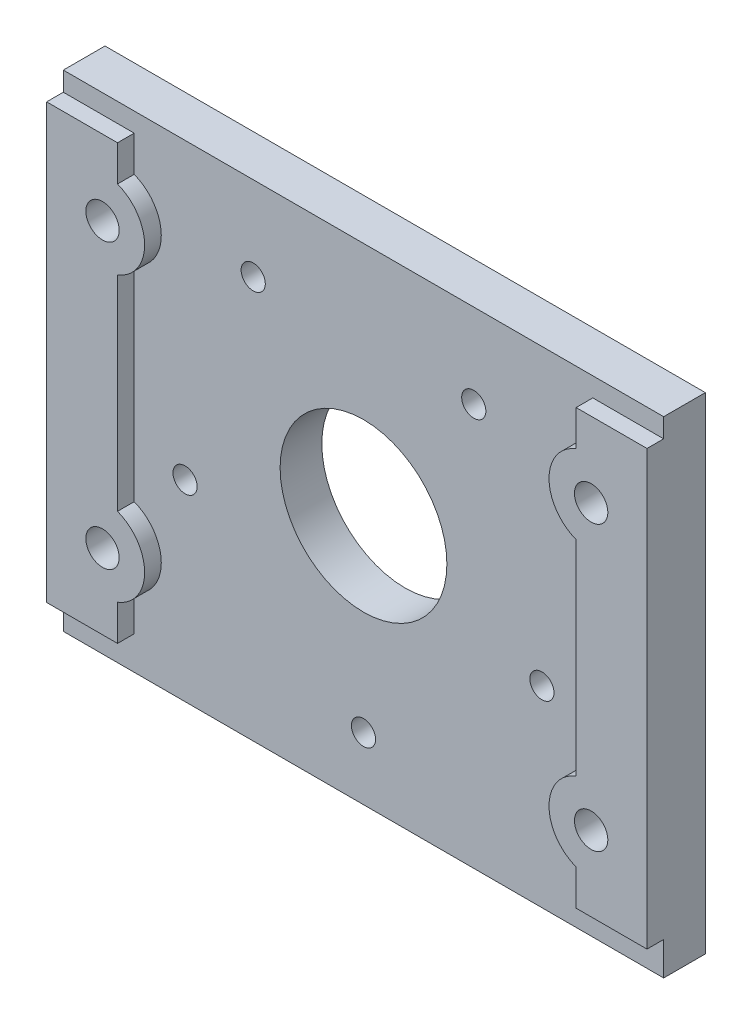
SolidWorks part; units mm, degrees
ref_plane "Front Plane" through (0, 0, 0) normal (0, 0, 1) x (1, 0, 0)
ref_plane "Top Plane" through (0, 0, 0) normal (0, 1, 0) x (1, 0, 0)
ref_plane "Right Plane" through (0, 0, 0) normal (1, 0, 0) x (0, 0, -1)
ref_plane "Plane1" through (0, 0, 280) normal (0, 0, 1) x (1, 0, 0)
sketch "Sketch1" plane through (0, 0, 280) normal (0, 0, 1) x (1, 0, 0)
  line L0 (264, 270) -> (336, 270)
  line L1 (336, 270) -> (336, 328.3)
  line L2 (336, 328.3) -> (264, 328.3)
  line L3 (264, 328.3) -> (264, 270)
  circle A0 centre (300, 300) radius 10
  circle A1 centre (286.7748, 318.2029) radius 1.45
  circle A2 centre (278.6012, 293.0471) radius 1.45
  circle A3 centre (300, 277.5) radius 1.45
  circle A4 centre (321.3988, 293.0471) radius 1.45
  circle A5 centre (313.2252, 318.2029) radius 1.45
extrude "Boss-Extrude1" add sketch "Sketch1" along normal blind 5
sketch "Sketch2" plane through (0, 0, 280) normal (0, 0, 1) x (1, 0, 0)
  line L0 (264, 274) -> (272.5, 274)
  line L1 (272.5, 274) -> (272.5, 326)
  line L2 (272.5, 326) -> (264, 326)
  line L3 (264, 326) -> (264, 274)
extrude "Boss-Extrude2" add sketch "Sketch2" along normal blind 7
sketch "Sketch3" plane through (0, 0, 280) normal (0, 0, 1) x (1, 0, 0)
  circle A0 centre (270.7, 283) radius 5.05
extrude "Boss-Extrude3" add sketch "Sketch3" along normal blind 7
sketch "Sketch4" plane through (0, 0, 280) normal (0, 0, 1) x (1, 0, 0)
  circle A0 centre (270.7, 317) radius 5.05
extrude "Boss-Extrude4" add sketch "Sketch4" along normal blind 7
ref_plane "Plane2" through (0, 0, 280.3) normal (0, 0, 1) x (1, 0, 0)
sketch "Sketch5" plane through (0, 0, 280.3) normal (0, 0, 1) x (1, 0, 0)
  circle A0 centre (270.7, 283) radius 2
  circle A1 centre (270.7, 317) radius 2
extrude "Cut-Extrude1" cut sketch "Sketch5" along normal blind 6.7
sketch "Sketch6" plane through (0, 0, 280) normal (0, 0, 1) x (1, 0, 0)
  line L0 (327.5, 274) -> (336, 274)
  line L1 (336, 274) -> (336, 326)
  line L2 (336, 326) -> (327.5, 326)
  line L3 (327.5, 326) -> (327.5, 274)
extrude "Boss-Extrude5" add sketch "Sketch6" along normal blind 7
sketch "Sketch7" plane through (0, 0, 280) normal (0, 0, 1) x (1, 0, 0)
  circle A0 centre (329.3, 283) radius 5.05
extrude "Boss-Extrude6" add sketch "Sketch7" along normal blind 7
sketch "Sketch8" plane through (0, 0, 280) normal (0, 0, 1) x (1, 0, 0)
  circle A0 centre (329.3, 317) radius 5.05
extrude "Boss-Extrude7" add sketch "Sketch8" along normal blind 7
sketch "Sketch9" plane through (0, 0, 280.3) normal (0, 0, 1) x (1, 0, 0)
  circle A0 centre (329.3, 283) radius 2
  circle A1 centre (329.3, 317) radius 2
extrude "Cut-Extrude2" cut sketch "Sketch9" along normal blind 6.7
ref_plane "Plane3" through (300, 0, 0) normal (1, 0, 0) x (0, 0, -1)
ref_plane "Plane4" through (0, 300, 0) normal (0, 1, 0) x (1, 0, 0)
ref_axis "HIP_AXIS" through (300, 300, 287.35) along (0, 0, -1)
ref_plane "Plane5" through (0, 0, 300) normal (0, 0, 1) x (1, 0, 0)
ref_axis "ABAD_AXIS" through (339.6, 300, 300) along (-1, 0, 0)
